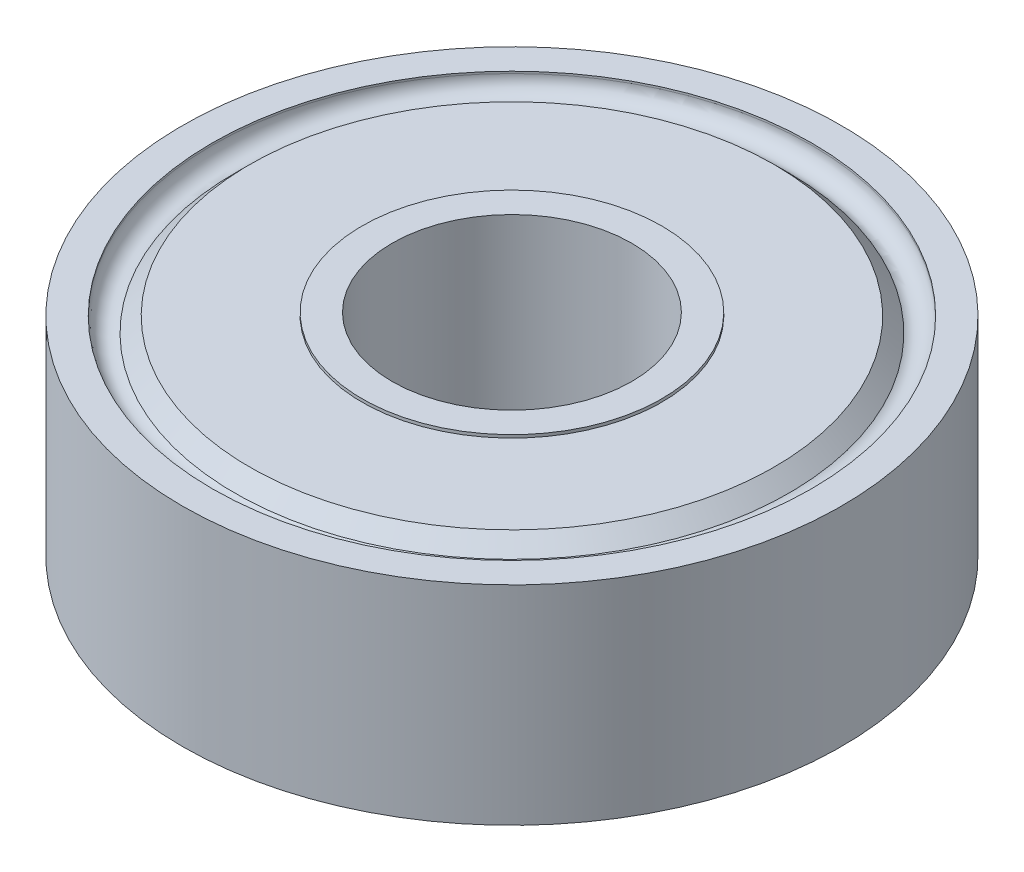
SolidWorks part; units mm, degrees
ref_plane "Спереди" through (0, 0, 0) normal (0, 0, 1) x (1, 0, 0)
ref_plane "Сверху" through (0, 0, 0) normal (0, 1, 0) x (1, 0, 0)
ref_plane "Справа" through (0, 0, 0) normal (1, 0, 0) x (0, 0, -1)
sketch "Эскиз1" plane through (0, 0, 0) normal (0, 1, 0) x (1, 0, 0)
  circle A0 centre (0, 0) radius 11
  dimension "D1" = 22
extrude "Бобышка-Вытянуть1" add sketch "Эскиз1" along normal blind 3.475 contours A0
sketch "Эскиз3" plane through (0, 0, 0) normal (0, -1, 0) x (1, 0, 0)
  circle A0 centre (0, 0) radius 10
  circle A1 centre (0, 0) radius 6
  circle A2 centre (0, 0) radius 8
  circle A3 centre (0, 0) radius 9.75
  dimension "D1" = 20
  dimension "D2" = 12
  dimension "D3" = 16
  dimension "D4" = 19.5
extrude "Вырез-Вытянуть2" cut sketch "Эскиз3" against normal blind 0.5 contours A0 A3 region at (-9.9717, 0, 0)
fillet "Скругление4" radius 0.5 1 edges at (0, 0.5, -10)
chamfer "Фаска1" distance 1 angle 45 1 edges at (0, 0, -9.75)
sketch "Эскиз7" plane through (0, 0, 0) normal (0, -1, 0) x (1, 0, 0)
  circle A0 centre (0, 0) radius 4
  dimension "D1" = 8
extrude "Вырез-Вытянуть3" cut sketch "Эскиз7" against normal through all and the other way through all
sketch "Эскиз15" plane through (0, 0, 0) normal (0, -1, 0) x (1, 0, 0)
  circle A0 centre (0, 0) radius 5
  dimension "D1" = 10
extrude "Бобышка-Вытянуть7" add sketch "Эскиз15" along normal blind 0.1
sketch "Эскиз18" plane through (0, -0.1, 0) normal (0, -1, 0) x (1, 0, 0)
  circle A0 centre (0, 0) radius 4
  dimension "D1" = 8
extrude "Вырез-Вытянуть4" cut sketch "Эскиз18" against normal through all
mirror "Зеркальное отражение3" about plane through (0, 3.475, 0) normal (0, 1, 0) of "Вырез-Вытянуть3", "Фаска1", "Скругление4", "Бобышка-Вытянуть1", "Вырез-Вытянуть2", "Бобышка-Вытянуть7"
sketch "Эскиз19" plane through (0, 7.05, 0) normal (0, 1, 0) x (1, 0, 0)
  circle A0 centre (0, 0) radius 4
  dimension "D1" = 8
extrude "Вырез-Вытянуть5" cut sketch "Эскиз19" against normal through all
